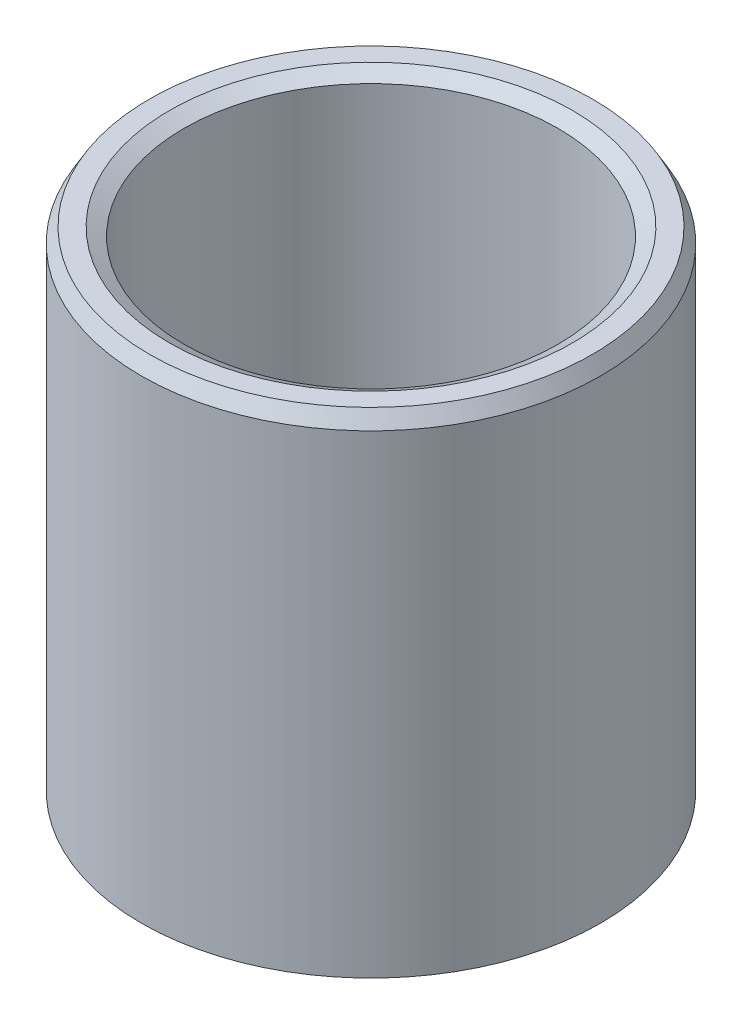
SolidWorks part; units mm, degrees
ref_plane "Front Plane" through (0, 0, 0) normal (0, 0, 1) x (1, 0, 0)
ref_plane "Top Plane" through (0, 0, 0) normal (0, 1, 0) x (1, 0, 0)
ref_plane "Right Plane" through (0, 0, 0) normal (1, 0, 0) x (0, 0, -1)
sketch "Sketch1" plane through (0, 0, 0) normal (0, 1, 0) x (1, 0, 0)
  circle A0 centre (0, 0) radius 22.5
  dimension "SLEEVE_OD" = 45
extrude "Boss-Extrude1" add sketch "Sketch1" along normal blind 48.6576
sketch "Sketch2" plane through (0, 0, 0) normal (0, 1, 0) x (1, 0, 0)
  circle A0 centre (0, 0) radius 18.322
  dimension "BORE_D" = 36.6441
extrude "Cut-Extrude1" cut sketch "Sketch2" along normal through all
chamfer "Chamfer1" distance 1.4134 angle 30 4 edges at (0, 48.6576, 18.322) (0, 0, 18.322) (0, 0, 22.5) (0, 48.6576, 22.5) first distance on face at (0, 48.6576, 18.322) first distance on face at (0, 0, 18.322) first distance on face at (0, 48.6576, 22.5)
